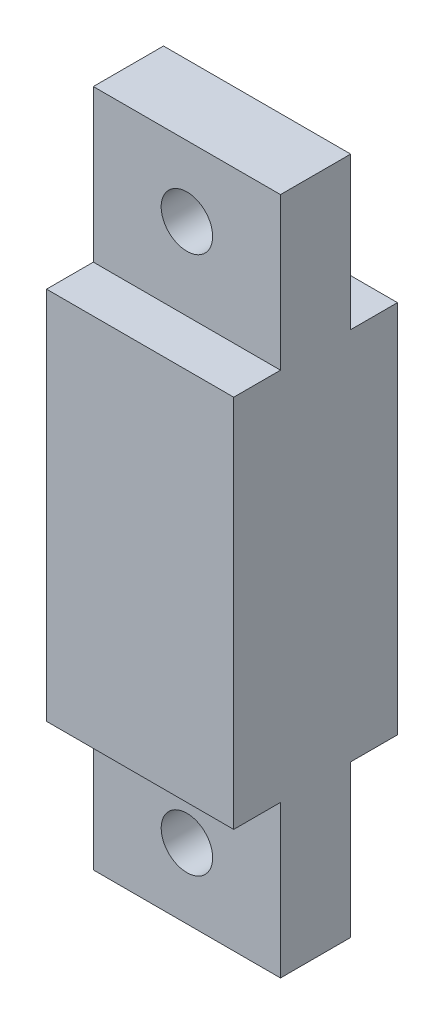
SolidWorks part; units mm, degrees
ref_plane "前视基准面" through (0, 0, 0) normal (0, 0, 1) x (1, 0, 0)
ref_plane "上视基准面" through (0, 0, 0) normal (0, 1, 0) x (1, 0, 0)
ref_plane "右视基准面" through (0, 0, 0) normal (1, 0, 0) x (0, 0, -1)
sketch "草图1" plane through (0, 0, 0) normal (0, 0, 1) x (1, 0, 0)
  line L1 (-4, 14.5) -> (4, 14.5)
  line L2 (-4, 14.5) -> (-4, -14.5)
  line L3 (-4, -14.5) -> (4, -14.5)
  line L4 (4, 14.5) -> (4, -14.5)
  line L5 (-4, 14.5) -> (4, -14.5) construction
  line L6 (-4, -14.5) -> (4, 14.5) construction
  point P0 (0, 0)
  dimension "D1" = 8
  dimension "D2" = 29
extrude "主体" add sketch "草图1" along normal blind 3
sketch "草图2" plane through (0, 0, 0) normal (0, 0, 1) x (1, 0, 0)
  line L0 (4, -14.5) -> (4, 14.5) construction
  line L1 (4, 8) -> (-4, 8)
  line L2 (4, 8) -> (4, -8)
  line L3 (4, -8) -> (-4, -8)
  line L4 (-4, 8) -> (-4, -8)
  line L5 (4, 8) -> (-4, -8) construction
  line L6 (4, -8) -> (-4, 8) construction
  point P0 (0, 0)
  dimension "D1" = 16
extrude "接线柱" add sketch "草图2" against normal blind 2
extrude "触点" add sketch "草图2<2>" along normal blind 2 from surface starting at face at (0, 0, 3)
sketch "草图2<2>" plane through (0, 0, 0) normal (0, 0, 1) x (1, 0, 0) same geometry as "草图2"
sketch "草图3" plane through (0, 0, 3) normal (0, 0, 1) x (1, 0, 0)
  line L0 (0, -3.85) -> (0, 3.85) construction
  line L1 (4, 14.5) -> (-4, 14.5) construction
  line L2 (3.85, 0) -> (-3.85, 0) construction
  circle A0 centre (0, 11.5) radius 1.1
  circle A1 centre (0, -11.5) radius 1.1
  dimension "D2" = 2.2
  dimension "D1" = 3
extrude "螺丝孔" cut sketch "草图3" against normal up to next
